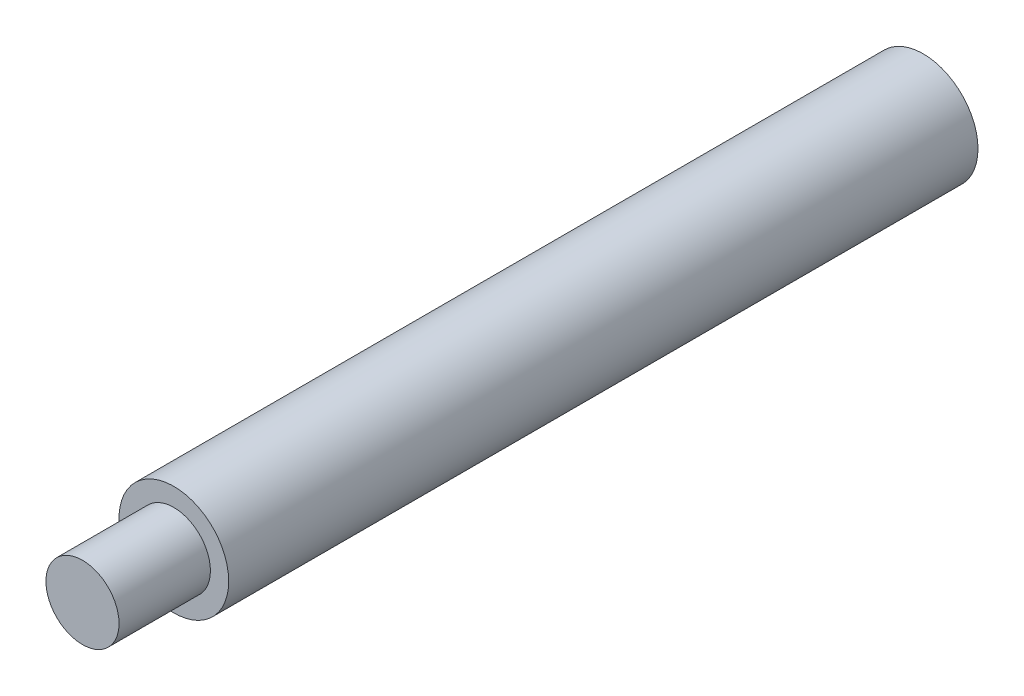
SolidWorks part; units mm, degrees
ref_plane "Front Plane" through (0, 0, 0) normal (0, 0, 1) x (1, 0, 0)
ref_plane "Top Plane" through (0, 0, 0) normal (0, 1, 0) x (1, 0, 0)
ref_plane "Right Plane" through (0, 0, 0) normal (1, 0, 0) x (0, 0, -1)
sketch "Sketch1" plane through (0, 0, 0) normal (0, 0, 1) x (1, 0, 0)
  circle A0 centre (0, 0) radius 1
  circle A1 centre (0, 0) radius 1.5
  dimension "D1" = 3
  dimension "D2" = 2
extrude "Boss-Extrude1" add sketch "Sketch1" along normal blind 2.5 contours A0
extrude "Boss-Extrude2" add sketch "Sketch1<3>" against normal blind 20.5 contours A1
sketch "Sketch1<3>" plane through (0, 0, 0) normal (0, 0, 1) x (1, 0, 0) same geometry as "Sketch1"
